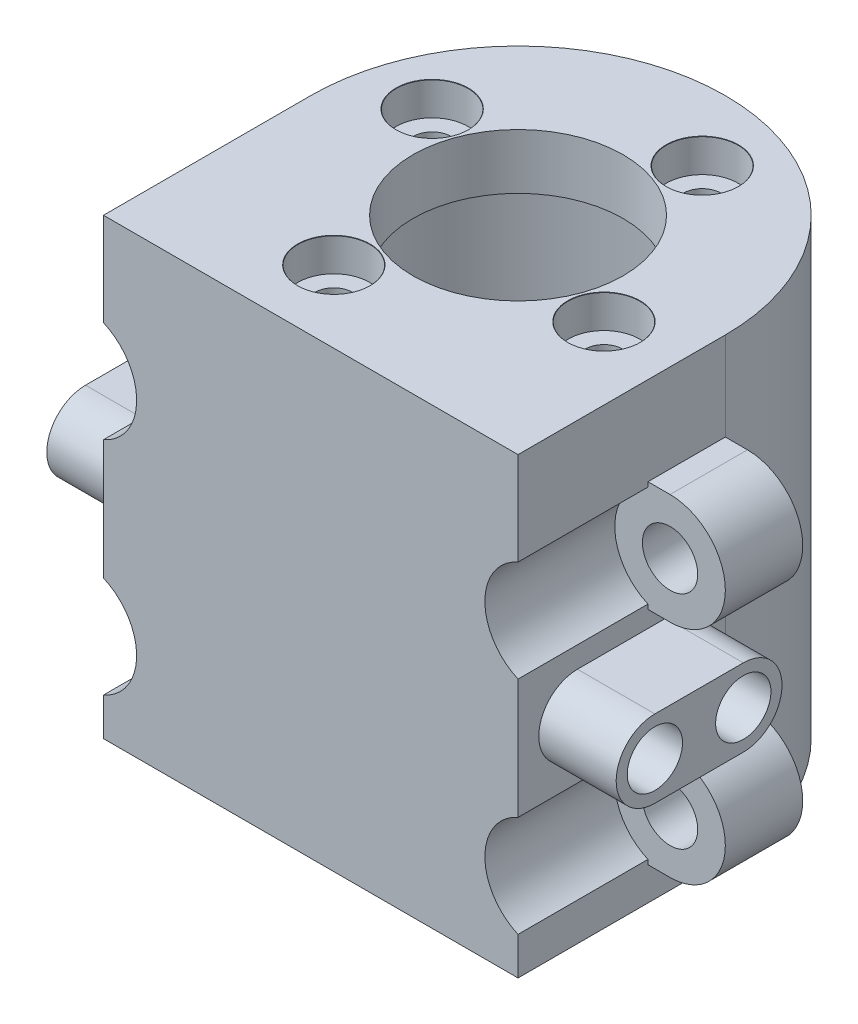
SolidWorks part; units mm, degrees
note: The reader was unsure of these and kept them because the rebuilt part matched: shared geometry of "Sketch2<5>", "Sketch2<7>".
ref_plane "Front Plane" through (0, 0, 0) normal (0, 0, 1) x (1, 0, 0)
ref_plane "Top Plane" through (0, 0, 0) normal (0, 1, 0) x (1, 0, 0)
ref_plane "Right Plane" through (0, 0, 0) normal (1, 0, 0) x (0, 0, -1)
sketch "Sketch1" plane through (0, 0, 0) normal (0, 1, 0) x (1, 0, 0)
  line L0 (-18.75, 0) -> (-18.75, -18.75)
  line L1 (-18.75, -18.75) -> (18.75, -18.75)
  line L2 (18.75, -18.75) -> (18.75, 0)
  circle A0 centre (0, 0) radius 16.2
  circle A1 centre (0, 0) radius 18.75
  dimension "D1" = 32.4
  dimension "D2" = 37.5
extrude "Boss-Extrude1" add sketch "Sketch1" along normal blind 36 contours A1 L0 L1 | A1 A0 | A1 L1 L2
ref_plane "Plane1" through (0, 0, 0) normal (0, 0, -1) x (-1, 0, 0)
sketch "Sketch2" plane through (0, 0, 0) normal (0, 0, 1) x (1, 0, 0)
  line L0 (-1018.75, 18) -> (48981.25, 18) construction
  line L1 (-18.75, 36) -> (-18.75, 0) construction
  line L2 (18.75, 36) -> (18.75, 0) construction
  line L3 (20.75, 33) -> (18.75, 33)
  line L4 (18.75, 33) -> (18.75, 23)
  line L5 (18.75, 23) -> (20.75, 23)
  line L6 (18.75, 13) -> (20.75, 13)
  line L7 (18.75, 3) -> (18.75, 13)
  line L8 (20.75, 3) -> (18.75, 3)
  circle A0 centre (20.75, 28) radius 2.5
  circle A1 centre (20.75, 28) radius 5
  circle A2 centre (20.75, 8) radius 5
  circle A3 centre (20.75, 8) radius 2.5
  point P5 (-18.75, 18)
  dimension "D1" = 5
  dimension "D2" = 10
  dimension "D3" = 10
  dimension "D4" = 2
extrude "Boss-Extrude2" add sketch "Sketch2" along normal blind 7 contours L3 A1 L4 | A1 L4 A0 | A0 | A2 L7 L6 | L7 A2 A3 | A3 | A2 L8 L7 | L4 A1 L5
extrude "Cut-Extrude2" cut sketch "Sketch2<5>" against normal up to surface (18.75 mm away) from surface contours A1 L4 | L7 A2 | A0 L4 | L7 A3
sketch "Sketch2<5>" plane through (0, 0, 0) normal (0, 0, 1) x (1, 0, 0) same geometry as "Sketch2"
extrude "Cut-Extrude5" cut sketch "Sketch2<7>" against normal blind 5 from surface at 7 contours A0 L4 | A0 L4 | L7 A3 | L7 A3 starting at face at (19.75, 28, 7)
sketch "Sketch2<7>" plane through (0, 0, 0) normal (0, 0, 1) x (1, 0, 0) same geometry as "Sketch2"
sketch "Sketch8" plane through (18.75, 0, 0) normal (1, 0, 0) x (0, 0, -1)
  line L0 (-13.375, 18) -> (-5.375, 18) construction
  line L1 (-18.75, 23.4174) -> (-18.75, 12.5826) construction
  line L2 (-13.375, 21.5) -> (-5.375, 21.5)
  line L3 (-13.375, 14.5) -> (-5.375, 14.5)
  line L4 (-18.75, 18) -> (0, 18) construction
  line L5 (0, -19.8) -> (0, 19.8) construction
  arc A0 (-13.375, 21.5) -> (-13.375, 14.5) centre (-13.375, 18) ccw
  arc A1 (-5.375, 14.5) -> (-5.375, 21.5) centre (-5.375, 18) ccw
  circle A2 centre (-13.375, 18) radius 2.5
  circle A3 centre (-5.375, 18) radius 2.5
  point P4 (-9.375, 18)
  point P9 (-18.75, 18)
  point P10 (-9.375, 18)
  dimension "D1" = 5
  dimension "D3" = 3.5
  dimension "D2" = 8
extrude "Boss-Extrude5" add sketch "Sketch8" along normal blind 7
mirror "Mirror1" about plane through (0, 0, 0) normal (1, 0, 0) of "Cut-Extrude5", "Cut-Extrude2", "Boss-Extrude2", "Boss-Extrude5"
sketch "Sketch3" plane through (0, 36, 0) normal (0, 1, 0) x (1, 0, 0)
  line L3 (-18.75, -18.75) -> (18.75, -18.75)
  line L4 (18.75, -18.75) -> (18.75, 0)
  line L5 (-18.75, 0) -> (-18.75, -18.75)
  line L6 (-18.75, -18.75) -> (18.75, -18.75)
  line L7 (18.75, -18.75) -> (18.75, 0)
  line L8 (-18.75, 0) -> (-18.75, -18.75)
  arc A1 (18.75, 0) -> (-18.75, 0) centre (0, 0) ccw
  arc A2 (18.75, 0) -> (-18.75, 0) centre (0, 0) ccw
  dimension "D1" = 0
extrude "Boss-Extrude4" add sketch "Sketch3" along normal blind 5
sketch "Sketch4" plane through (0, 41, 0) normal (0, 1, 0) x (1, 0, 0)
  circle A0 centre (0, 0) radius 9.5
  dimension "D1" = 19
extrude "Cut-Extrude3" cut sketch "Sketch4" against normal up to next
sketch "Sketch5" plane through (0, 41, 0) normal (0, 1, 0) x (1, 0, 0)
  line L0 (0, -1000) -> (0, 49000) construction
  line L1 (0, 0) -> (4.4463, 12.216) construction
  line L2 (0, 0) -> (4.4463, 12.216) construction
  circle A0 centre (0, 0) radius 13 construction
  point P3 (4.4463, 12.216)
  point P10 (12.216, -4.4463)
  point P11 (-4.4463, -12.216)
  point P12 (-12.216, 4.4463)
  dimension "D1" = 26
  dimension "D2" = 20
  dimension "D3" = 4
hole_wizard "CBORE for M3 SHCS1" positions "Sketch5" profile "Sketch6" counterbore size "M3" standard "ANSI Metric" end condition through all
sketch "Sketch6" plane through (-12.216, 41, -4.4463) normal (1, 0, 0) x (0, 0, 1)
  line L0 (0, 0) -> (0, 41)
  line L1 (0, 41) -> (1.7, 41)
  line L3 (1.7, 41) -> (1.7, 3)
  line L4 (3.25, 3) -> (1.7, 3)
  line L5 (3.25, 3) -> (3.25, 0.025)
  line L6 (3.25, 0.025) -> (3.275, 0)
  line L7 (3.275, 0) -> (0, 0)
  line L8 (-3.25, 0.025) -> (-3.275, 0) construction
  line L11 (0, -6.35) -> (0, 107.95) construction
  dimension "Thru Hole Dia." = 3.4
  dimension "Thru Hole Depth" = 41
  dimension "C'Bore Dia." = 6.5
  dimension "C'Bore Depth" = 3
  dimension "Near C'Sink Dia." = 6.55
  dimension "Near C'Sink Angle" = 90
equation "\"m3_heat\"= 5"
equation "\"D1@Sketch2\"=\"m3_heat\""
equation "\"D1@Sketch8\"=\"m3_heat\""
